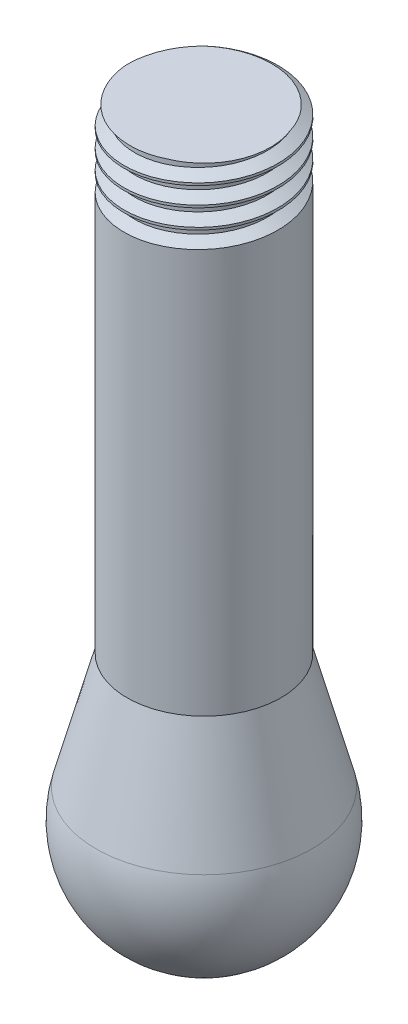
SolidWorks part; units mm, degrees
ref_plane "Plan de face" through (0, 0, 0) normal (0, 0, 1) x (1, 0, 0)
ref_plane "Plan de dessus" through (0, 0, 0) normal (0, 1, 0) x (1, 0, 0)
ref_plane "Plan de droite" through (0, 0, 0) normal (1, 0, 0) x (0, 0, -1)
sketch "Esquisse1" plane through (0, 0, 0) normal (0, 0, 1) x (1, 0, 0)
  line L0 (4, 7.5) -> (5.6071, 1.5024)
  line L2 (0, -5.8048) -> (0, 32)
  line L3 (0, 32) -> (4, 32)
  line L4 (4, 7.5) -> (4, 32)
  arc A0 (5.6071, 1.5024) -> (0, -5.8048) centre (0, 0) cw
  dimension "D1" = 4
  dimension "D2" = 32
  dimension "D3" = 15
  dimension "D4" = 7.5
revolve "Révolution1" add sketch "Esquisse1" angle 360 about L2
thread "Filetage1" pitch 1 method cut trim with start face yes trim with end face yes profile "Profil de filetage1" start angle 0, offset 1, length 4, pitch 1, diameter 8
ref_plane "Plan1" through (-4, 33, 0) normal (0, 0, 1) x (-1, 0, 0)
sketch "Profil de filetage1" plane through (-4, 33, 0) normal (0, 0, 1) x (-1, 0, 0)
  line L0 (0, 0) -> (0, 1) construction
  line L11 (0, 0) -> (0, 0.875)
  line L12 (0, 0.875) -> (-0.5413, 0.5625)
  line L13 (-0.5413, 0.5625) -> (-0.5413, 0.3125)
  line L15 (-0.5413, 0.3125) -> (0, 0)
  line L17 (-0.5413, 0.4375) -> (0, 0.4375) construction
  point P2 (0, 0)
  dimension "Pitch" = 1
  dimension "Profile_Angle" = 60
  dimension "Profile_Land" = 0.25
  dimension "Profile_Height" = 0.5413
